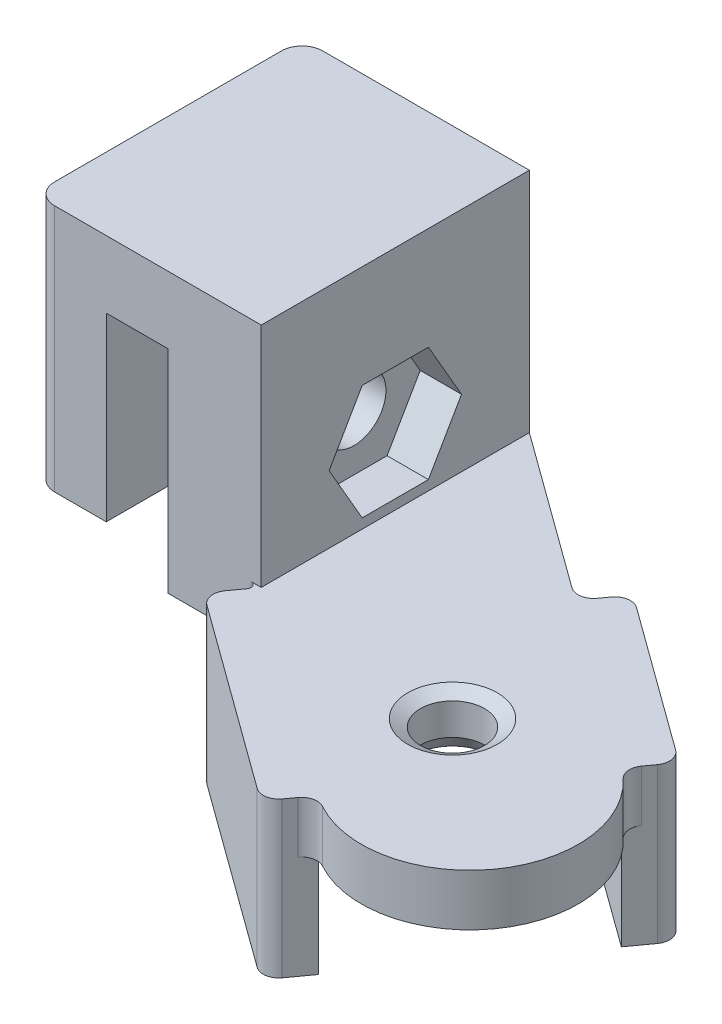
SolidWorks part; units mm, degrees
note: The reader was unsure of these and kept them because the rebuilt part matched: shared geometry of "草图5<3>".
material "PA 类型 6"
ref_plane "前视基准面" through (0, 0, 0) normal (0, 0, 1) x (1, 0, 0)
ref_plane "上视基准面" through (0, 0, 0) normal (0, 1, 0) x (1, 0, 0)
ref_plane "右视基准面" through (0, 0, 0) normal (1, 0, 0) x (0, 0, -1)
sketch "草图1" plane through (0, 0, 0) normal (0, 1, 0) x (1, 0, 0)
  line L0 (0, 0) -> (0, 12.2017) construction
  line L1 (0, 0) -> (15.21, 0) construction
  line L2 (0, 0) -> (11.3188, 8.2236) construction
  line L5 (6.1542, 2.018) -> (-0.0175, -6.4766) construction
  line L7 (-10.1244, 13.8452) -> (6.1542, 2.018)
  line L8 (-10.1244, 0.8664) -> (-0.0175, -6.4766)
  line L9 (-10.1244, 13.8452) -> (-10.1244, 0.8664)
  line L10 (0, 0) -> (-11.3188, 8.2236) construction
  circle A0 centre (0, 0) radius 1.55
  arc A2 (6.1542, 2.018) -> (-0.0175, -6.4766) centre (3.0684, -2.2293) cw
  dimension "D1" = 3.1
  dimension "D5" = 5.25
  dimension "D2" = 36
  dimension "D6" = 10.1244
  dimension "D7" = 5.25
extrude "基座" add sketch "草图1" along normal blind 2.5
sketch "草图2" plane through (0, 0, 0) normal (0, 1, 0) x (1, 0, 0)
  line L3 (6.1542, 2.018) -> (-10.1244, 13.8452) construction
  line L5 (0, 0) -> (19.4408, 0) construction
  line L6 (6.1542, 2.018) -> (-10.1244, 13.8452) construction
  line L7 (0, 0) -> (0, 16.8119) construction
  line L14 (0, 0) -> (-14.65, 10.6439) construction
  line L15 (-11.3, -0.7516) -> (-10.1244, 0.8664)
  line L16 (-1.1931, -8.0947) -> (-11.3, -0.7516)
  line L17 (-0.0175, -6.4766) -> (-1.1931, -8.0947)
  line L18 (-10.1244, 0.8664) -> (-0.0175, -6.4766)
  line L19 (7.3298, 3.6361) -> (-0.8095, 9.5496)
  line L20 (6.1542, 2.018) -> (7.3298, 3.6361)
  line L21 (-1.9851, 7.9316) -> (6.1542, 2.018)
  line L22 (-0.8095, 9.5496) -> (-1.9851, 7.9316)
  point P6 (-1.9851, 7.9316)
  dimension "D1" = 36
  dimension "D2" = 2
extrude "机臂限位" add sketch "草图2" against normal blind 7.5 from surface at 2.5 contours L18 L15 L16 L17 | L19 L22 L21 L20 starting at face at (-2.4662, 2.5, -1.7918)
sketch "草图3" plane through (0, 0, 0) normal (0, 1, 0) x (1, 0, 0)
  line L0 (-14.6244, 13.8452) -> (-10.1244, 13.8452)
  line L1 (-10.1244, 13.8452) -> (-10.1244, 0.8664)
  line L2 (-10.1244, 0.8664) -> (-14.6244, 0.8664)
  line L3 (-14.6244, 0.8664) -> (-14.6244, 13.8452)
  dimension "D1" = 4.5
extrude "限位-1" add sketch "草图3" along normal blind 13.5
sketch "草图4" plane through (0, 0, 0) normal (0, 0, 1) x (1, 0, 0)
  line L7 (-14.6244, 13.5) -> (-14.6244, 0) construction
  line L10 (-14.6244, 10.25) -> (-14.6244, 13.5)
  line L11 (-17.6244, 10.25) -> (-14.6244, 10.25)
  line L12 (-17.6244, 1.5) -> (-17.6244, 10.25)
  line L13 (-21.1244, 1.5) -> (-17.6244, 1.5)
  line L14 (-21.1244, 13.5) -> (-21.1244, 1.5)
  line L15 (-14.6244, 13.5) -> (-21.1244, 13.5)
  line L16 (-10.1244, 13.5) -> (-14.6244, 13.5) construction
  dimension "D5" = 3
  dimension "D6" = 3.5
  dimension "D7" = 3.25
  dimension "D8" = 8.75
extrude "限位-2" add sketch "草图4" against normal up to surface (12.9787 mm away) from surface at -0.8664 up to face at (-11.9244, 5.9, -13.8452) starting at face at (-11.9244, 5.9, -0.8664)
sketch "草图5" plane through (-21.1244, 0, 0) normal (1, 0, 0) x (0, 0, -1)
  line L2 (7.3558, 13.5) -> (7.3558, 5.75) construction
  line L5 (8.9579, 2.975) -> (10.5601, 5.75)
  line L6 (10.5601, 5.75) -> (8.9579, 8.525)
  line L7 (8.9579, 8.525) -> (5.7537, 8.525)
  line L8 (5.7537, 8.525) -> (4.1515, 5.75)
  line L9 (4.1515, 5.75) -> (5.7537, 2.975)
  line L10 (5.7537, 2.975) -> (8.9579, 2.975)
  line L14 (13.8452, 13.5) -> (0.8664, 13.5) construction
  circle A0 centre (7.3558, 5.75) radius 1.55
  circle A1 centre (7.3558, 5.75) radius 2.775 construction
  dimension "D1" = 3.1
  dimension "D2" = 5.55
  dimension "D3" = 7.75
extrude "螺丝位" cut sketch "草图5" along normal through all contours A0
extrude "螺母位" cut sketch "草图5<3>" against normal blind 2 from surface at 11 contours L10 L9 L8 L7 L6 L5 A0 starting at face at (-10.1244, 5.75, -5.8058)
sketch "草图5<3>" plane through (-21.1244, 0, 0) normal (1, 0, 0) x (0, 0, -1) same geometry as "草图5"
chamfer "倒角1" distance 0.615 angle 30 3 edges at (0, 2.5, 1.55) (0, 0, 1.55) (-21.1244, 5.75, -5.8058)
fillet "圆角5" radius 0.75 7 edges at (-0.8095, -1.25, -9.5496) (7.3298, -1.25, -3.6361) (-1.1931, -1.25, 8.0947) (-11.3, -1.25, 0.7516) (-1.9851, 1.25, -7.9316) (6.1542, 1.25, -2.018) (-0.0175, 1.25, 6.4766)
fillet "圆角6" radius 0.25 1 edges at (-10.1244, 1.25, -0.8664)
fillet "圆角8" radius 1 2 edges at (-21.1244, 7.5, -0.8664) (-21.1244, 7.5, -13.8452)
